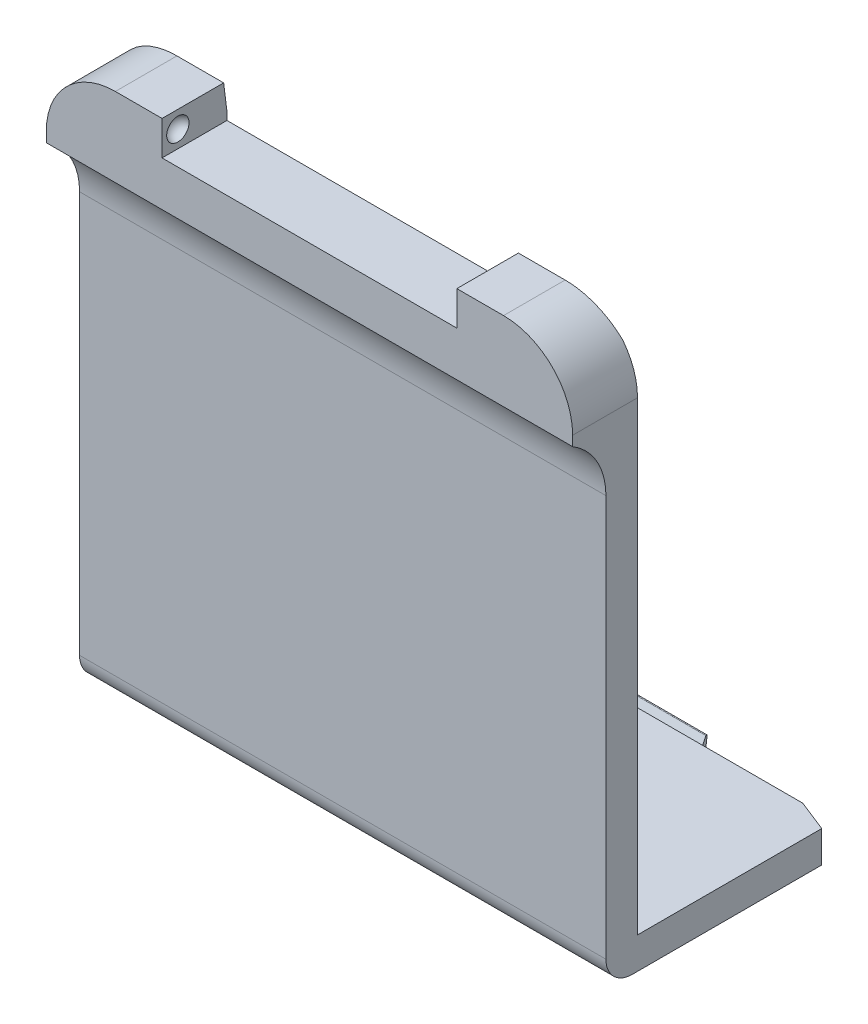
SolidWorks part; units mm, degrees
ref_plane "Front Plane" through (0, 0, 0) normal (0, 0, 1) x (1, 0, 0)
ref_plane "Top Plane" through (0, 0, 0) normal (0, 1, 0) x (1, 0, 0)
ref_plane "Right Plane" through (0, 0, 0) normal (1, 0, 0) x (0, 0, -1)
sketch "Sketch1" plane through (0, 0, 0) normal (0, 0, 1) x (1, 0, 0)
  line L1 (0, 0) -> (40, 0)
  line L2 (0, 0) -> (0, 40.6)
  line L3 (0, 40.6) -> (40, 40.6)
  line L4 (40, 0) -> (40, 40.6)
  dimension "D1" = 40
  dimension "D2" = 40.6
extrude "Boss-Extrude1" add sketch "Sketch1" along normal blind 2.4
sketch "Sketch2" plane through (0, 0, 2.4) normal (0, 0, 1) x (1, 0, 0)
  line L1 (0, 0) -> (40, 0)
  line L2 (0, 0) -> (0, -2.4)
  line L3 (0, -2.4) -> (40, -2.4)
  line L4 (40, 0) -> (40, -2.4)
  dimension "D1" = 2.4
extrude "Boss-Extrude2" add sketch "Sketch2" against normal blind 17.35
sketch "Sketch3" plane through (0, 0, 2.4) normal (0, 0, 1) x (1, 0, 0)
  line L0 (40, 40.6) -> (0, 40.6) construction
  line L1 (8.8, 40.6) -> (31.2, 40.6)
  line L2 (8.8, 40.6) -> (8.8, 38)
  line L3 (8.8, 38) -> (31.2, 38)
  line L4 (31.2, 40.6) -> (31.2, 38)
  line L5 (8.8, 38) -> (0, 40.6) construction
  line L6 (31.2, 38) -> (40, 40.6) construction
  dimension "D1" = 22.4
  dimension "D2" = 2.6
extrude "Cut-Extrude1" cut sketch "Sketch3" against normal up to surface (2.4 mm away) up to face at (15, 20.3, 0)
ref_plane "Plane1" through (20, 0, 0) normal (-1, 0, 0) x (0, 0, 1)
sketch "Sketch5" plane through (0, 0, 2.4) normal (0, 0, 1) x (1, 0, 0)
  line L0 (0, 34.6) -> (40, 34.6)
  line L8 (40, 40.6) -> (31.2, 40.6)
  line L9 (31.2, 40.6) -> (31.2, 38)
  line L10 (31.2, 38) -> (8.8, 38)
  line L11 (8.8, 38) -> (8.8, 40.6)
  line L12 (8.8, 40.6) -> (0, 40.6)
  line L13 (0, 40.6) -> (0, -2.4)
  line L14 (0, -2.4) -> (40, -2.4)
  line L15 (40, -2.4) -> (40, 40.6)
  line L16 (40, 40.6) -> (31.2, 40.6)
  line L17 (31.2, 40.6) -> (31.2, 38)
  line L18 (31.2, 38) -> (8.8, 38)
  line L19 (8.8, 38) -> (8.8, 40.6)
  line L20 (8.8, 40.6) -> (0, 40.6)
  line L21 (0, 40.6) -> (0, -2.4)
  line L22 (0, -2.4) -> (40, -2.4)
  line L23 (40, -2.4) -> (40, 40.6)
  line M10 (40, 40.6) -> (31.2, 40.6)
  line M11 (31.2, 40.6) -> (31.2, 38)
  line M12 (31.2, 38) -> (8.8, 38)
  line M13 (8.8, 38) -> (8.8, 40.6)
  line M14 (8.8, 40.6) -> (0, 40.6)
  line M15 (0, 40.6) -> (0, -2.4)
  line M17 (40, -2.4) -> (40, 40.6)
  dimension "D2" = 6
  dimension "D1" = 0
extrude "Boss-Extrude3" add sketch "Sketch5" along normal blind 2.53 contours L0 M15 M17 M10 M11 M12 M13 M14 region at (20, 37.0553, 2.4)
sketch "Sketch4" plane through (8.8, 0, 0) normal (1, 0, 0) x (0, 0, -1)
  line L3 (-2.88, 39.3) -> (-4.58, 39.3)
  line L4 (-4.93, 38) -> (-4.93, 40.6) construction
  arc A0 (-4.58, 39.3) -> (-2.88, 39.3) centre (-3.73, 39.3) ccw
  dimension "D1" = 1.7
  dimension "D2" = 1.2
revolve "Cut-Revolve2" cut sketch "Sketch4" angle 360 about L3
mirror "Mirror2" about plane through (20, 0, 0) normal (-1, 0, 0) of "Cut-Revolve2"
fillet "Fillet1" radius 5.25 2 edges at (0, 40.6, 2.465) (40, 40.6, 2.465)
fillet "Fillet2" radius 5.25 1 edges
sketch "Sketch6" plane through (31.2, 0, 0) normal (-1, 0, 0) x (0, 0, 1)
  line L0 (0, 40.6) -> (0, 38.6)
  line L1 (0, 40.6) -> (4.93, 40.6) construction
  line L2 (0.25, 40.6) -> (0, 40.6)
  line L4 (0, 38) -> (0, 40.6) construction
  line L5 (0, 38.6) -> (0.25, 40.6)
  dimension "D1" = 0.25
  dimension "D2" = 2
extrude "Cut-Extrude2" cut sketch "Sketch6" against normal blind 16.4
mirror "Mirror3" about plane through (20, 0, 0) normal (-1, 0, 0) of "Cut-Extrude2"
fillet "Fillet3" radius 2 1 edges at (20, -2.4, 2.4)
sketch "Sketch7" plane through (0, 0, 0) normal (0, 1, 0) x (1, 0, 0)
  line L0 (37.6, 14.952) -> (40, 14)
  line L1 (40, 14) -> (36.1823, 15.5144) construction
  line L2 (40, 14) -> (37.6, 14.952) construction
  line L3 (40, 14) -> (40, 14.95)
  line L4 (40, 14.95) -> (37.6, 14.952)
extrude "Cut-Extrude3" cut sketch "Sketch7" against normal through all
ref_plane "Plane2" through (20, 0, 0) normal (-1, 0, 0) x (0, 0, 1)
sketch "Sketch8" plane through (20, 0, 0) normal (-1, 0, 0) x (0, 0, 1)
  line L0 (-14.95, 0) -> (-15.323, 0.8)
  line L1 (-15.323, 0.8) -> (-14.95, -2.4)
  line L2 (-14.95, -2.4) -> (-14.95, 0)
  dimension "D1" = 155
  dimension "D2" = 0.8
extrude "Boss-Extrude4" add sketch "Sketch8" along normal blind 10 and the other way blind 10
fillet "Fillet4" radius 0.05 1 edges at (20, 0.8, -15.323)
